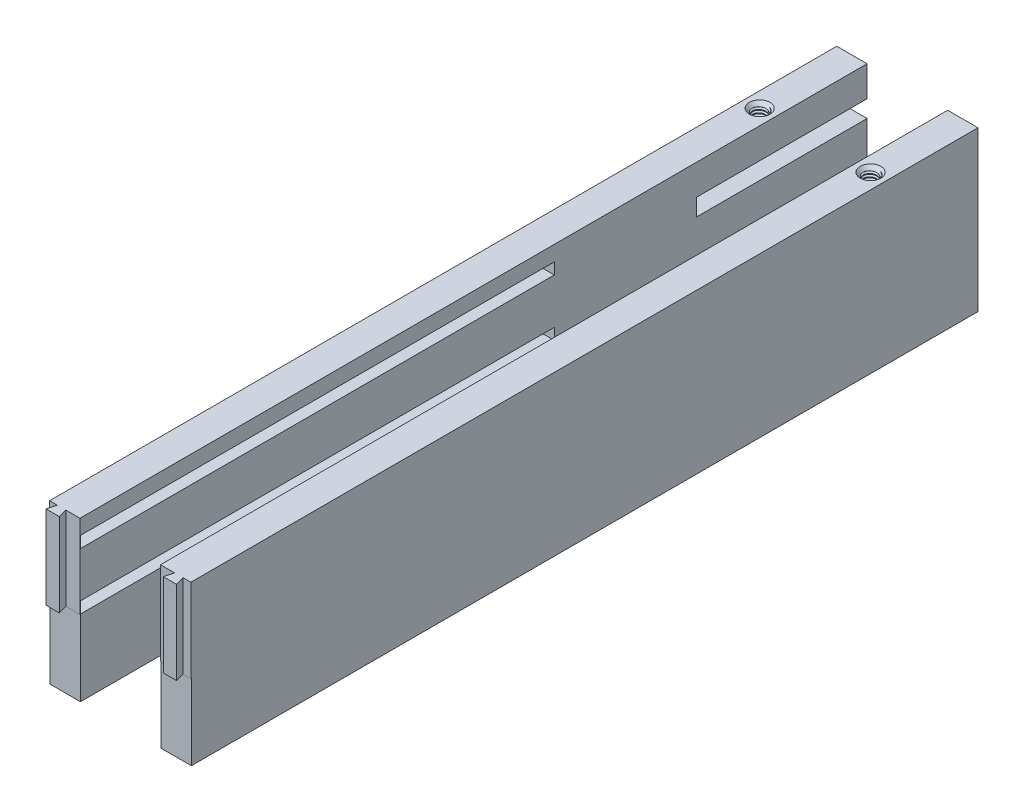
SolidWorks part; units mm, degrees
ref_plane "Front Plane" through (0, 0, 0) normal (0, 0, 1) x (1, 0, 0)
ref_plane "Top Plane" through (0, 0, 0) normal (0, 1, 0) x (1, 0, 0)
ref_plane "Right Plane" through (0, 0, 0) normal (1, 0, 0) x (0, 0, -1)
sketch "Sketch1" plane through (0, 0, 0) normal (1, 0, 0) x (0, 0, -1)
  line L1 (-64.8048, 9.1795) -> (145.1952, 9.1795)
  line L2 (-64.8048, 9.1795) -> (-64.8048, -32.8205)
  line L3 (-64.8048, -32.8205) -> (145.1952, -32.8205)
  line L4 (145.1952, 9.1795) -> (145.1952, -32.8205)
  dimension "D1" = 210
  dimension "D2" = 42
extrude "Boss-Extrude1" add sketch "Sketch1" along normal blind 8 contours L2 L3 L4 L1
sketch "Sketch12" plane through (0, 9.1795, 0) normal (0, 1, 0) x (1, 0, 0)
  line L0 (0, -62.4548) -> (2.0297, -62.4548)
  line L1 (0, -64.8048) -> (0, 145.1952) construction
  line L2 (2.0297, -62.4548) -> (1.4, -64.8048)
  line L3 (8, -64.8048) -> (0, -64.8048) construction
  line L4 (1.4, -64.8048) -> (0, -64.8048)
  line L5 (0, -64.8048) -> (0, -62.4548)
  line L6 (8, -62.4548) -> (8, -64.8048)
  line L7 (8, -64.8048) -> (8, 145.1952) construction
  line L8 (8, -64.8048) -> (4.9094, -64.8048)
  line L9 (4.9094, -64.8048) -> (4.2797, -62.4548)
  line L10 (4.2797, -62.4548) -> (8, -62.4548)
  dimension "D1" = 2.35
  dimension "D3" = 105
  dimension "D4" = 105
  dimension "D5" = 2.25
  dimension "D6" = 1.4
extrude "Cut-Extrude8" cut sketch "Sketch12" against normal blind 25
sketch "Sketch13" plane through (0, -32.8205, 0) normal (0, -1, 0) x (1, 0, 0)
  line L0 (8, 64.8048) -> (8, -145.1952) construction
  line L1 (0, 64.8048) -> (8, 64.8048)
  line L2 (0, 64.8048) -> (0, 62.3048)
  line L3 (0, 62.3048) -> (8, 62.3048)
  line L4 (8, 64.8048) -> (8, 62.3048)
  dimension "D1" = 2.5
extrude "Cut-Extrude9" cut sketch "Sketch13" against normal blind 20
sketch "Sketch43" plane through (8, 0, 0) normal (1, 0, 0) x (0, 0, -1)
  line L0 (145.1952, -32.8205) -> (145.1952, -27.8205) construction
  line L2 (145.1952, -27.8205) -> (140.1952, -27.8205) construction
  line L3 (140.1952, -27.8205) -> (140.1952, -12.8205)
  line L4 (140.1952, -12.8205) -> (135.1952, -12.8205)
  line L5 (135.1952, -12.8205) -> (135.1952, -27.8205)
  line L6 (135.1952, -27.8205) -> (140.1952, -27.8205)
  dimension "D1" = 15
  dimension "D2" = 5
  dimension "D3" = 5
  dimension "D4" = 5
extrude "Boss-Extrude8" add sketch "Sketch43" along normal blind 6
sketch "Sketch44" plane through (8, 0, 0) normal (1, 0, 0) x (0, 0, -1)
  line L0 (145.1952, -32.8205) -> (130.1952, -32.8205) construction
  line L1 (-62.3048, -32.8205) -> (145.1952, -32.8205) construction
  line L2 (130.1952, -32.8205) -> (130.1952, -26.8205)
  line L3 (130.1952, -26.8205) -> (115.1952, -26.8205)
  line L4 (115.1952, -26.8205) -> (115.1952, -32.8205)
  line L5 (115.1952, -32.8205) -> (130.1952, -32.8205)
  dimension "D1" = 15
  dimension "D2" = 15
  dimension "D3" = 6
extrude "Boss-Extrude9" add sketch "Sketch44" along normal blind 6
sketch "Sketch46" plane through (0, 0, 62.3048) normal (0, 0, 1) x (1, 0, 0)
  line L0 (8, 9.1795) -> (8, 5.1795) construction
  line L1 (8, -12.8205) -> (8, 9.1795) construction
  line L2 (8, 5.1795) -> (8, 2.1795)
  line L3 (8, 2.1795) -> (8, -9.7705) construction
  line L4 (8, -9.7705) -> (8, -12.7705)
  line L5 (8, 5.1795) -> (4.9094, 5.1795)
  line L6 (4.9094, -12.8205) -> (4.9094, 9.1795) construction
  line L7 (4.9094, 5.1795) -> (4.9094, 2.1795)
  line L8 (4.9094, 2.1795) -> (8, 2.1795)
  line L9 (8, -9.7705) -> (4.813, -9.7705)
  line L10 (4.813, -9.7705) -> (4.9094, -12.7705)
  line L11 (4.9094, -12.7705) -> (8, -12.7705)
  dimension "D1" = 4
  dimension "D2" = 3
  dimension "D3" = 11.95
  dimension "D4" = 3
extrude "Cut-Extrude15" cut sketch "Sketch46" against normal blind 125
ref_plane "Plane1" through (18.625, 0, 0) normal (-1, 0, 0) x (0, 0, 1)
sketch "Sketch23" plane through (0, 0, -145.1952) normal (0, 0, -1) x (-1, 0, 0)
  line L0 (-8, -32.8205) -> (-8, -3.3205)
  line L1 (-8, 9.1795) -> (-8, -32.8205) construction
  line L3 (-8, -3.3205) -> (-3.5, -3.3205)
  line L4 (-8, -3.3205) -> (-8, 1.1795)
  line L5 (-8, 1.1795) -> (-3.5, 1.1795)
  line L6 (-3.5, -3.3205) -> (-3.5, 1.1795)
  line M5 (-8, 9.1795) -> (-8, -32.8205)
  dimension "D1" = 4.5
  dimension "D2" = 4.5
  dimension "D3" = 29.5
extrude "Cut-Extrude14" cut sketch "Sketch23" against normal blind 45 contours L3 L6 L5 M5 region at (5.75, -1.0705, -145.1952)
mirror "Mirror4" about plane through (18.625, 0, 0) normal (-1, 0, 0) of bodies 121 113
sketch "Sketch30" plane through (0, 9.1795, 0) normal (0, 1, 0) x (1, 0, 0)
  line L0 (0, -62.4548) -> (0, 145.1952) construction
  line L1 (37.25, -62.4548) -> (37.25, 145.1952) construction
  line L2 (4, 120.8538) -> (33.25, 120.8538) construction
  circle A0 centre (4, 120.8538) radius 2
  circle A1 centre (33.25, 120.8538) radius 2
  dimension "D1" = 4
  dimension "D2" = 4
hole_wizard "#8-32 Tapped Hole1" positions "Sketch35" profile "Sketch37" tap size "#8-32" standard "ANSI Inch"
sketch "Sketch35" plane through (0, 9.1795, 0) normal (0, 1, 0) x (1, 0, 0)
  point P0 (33.25, 120.8538)
  point P3 (4, 120.8538)
sketch "Sketch37" plane through (33.25, 9.1795, -120.8538) normal (1, 0, 0) x (0, 0, 1)
  line L0 (0, 0) -> (0, 10.7074)
  line L1 (0, 10.7074) -> (1.7272, 9.6696)
  line L2 (1.7272, 9.6696) -> (1.7272, 0.9906)
  line L3 (1.7272, 0.9906) -> (2.7178, 0)
  line L5 (2.7178, 0) -> (0, 0)
  line L6 (-1.7272, 0.9906) -> (-2.7178, 0) construction
  line L10 (0, 10.7074) -> (-1.7272, 9.6696) construction
  line L11 (0, -6.35) -> (0, 107.95) construction
  dimension "Tap Drill Dia." = 3.4544
  dimension "Tap Drill Depth" = 10.7074
  dimension "Near C'Sink Dia." = 5.4356
  dimension "Near C'Sink Angle" = 90
  dimension "Drill Angle" = 118
cosmetic thread "Hole Thread2" parameters "D1"=8.33, "D2"=4.1656
cosmetic thread "Hole Thread6" parameters "D1"=8.33, "D2"=4.1656
thread "Thread3" pitch 0.7937 method cut profile "Thread Profile5" start angle 0, offset 1, length 10, pitch 0.7937, diameter 3.4544
ref_plane "Plane6" through (31.5228, 9.1889, -120.8538) normal (0, 0, 1) x (-1, 0, 0)
sketch "Thread Profile5" plane through (31.5228, 9.1889, -120.8538) normal (0, 0, 1) x (-1, 0, 0)
  line L0 (0, 0) -> (0, 0.7937) construction
  line L1 (0, 0) -> (0.4296, 0.248)
  line L2 (0.4296, 0.248) -> (0.4296, 0.3473)
  line L3 (0.4296, 0.3473) -> (0, 0.5953)
  line L4 (0.4296, 0.2977) -> (0, 0.2977) construction
  line L11 (0, 0) -> (0, 0.5953)
  point P2 (0, 0)
  dimension "Pitch" = 0.7937
  dimension "Profile_Angle" = 60
  dimension "Profile_Land" = 0.0992
  dimension "Profile_Height" = 0.4296
thread "Thread4" pitch 0.7937 method cut profile "Thread Profile6" start angle 0, offset 1, length 10, pitch 0.7937, diameter 3.4544
ref_plane "Plane7" through (2.2728, 9.1889, -120.8538) normal (0, 0, 1) x (-1, 0, 0)
sketch "Thread Profile6" plane through (2.2728, 9.1889, -120.8538) normal (0, 0, 1) x (-1, 0, 0)
  line L0 (0, 0) -> (0, 0.7937) construction
  line L1 (0, 0) -> (0.4296, 0.248)
  line L2 (0.4296, 0.248) -> (0.4296, 0.3473)
  line L3 (0.4296, 0.3473) -> (0, 0.5953)
  line L4 (0.4296, 0.2977) -> (0, 0.2977) construction
  line L11 (0, 0) -> (0, 0.5953)
  point P2 (0, 0)
  dimension "Pitch" = 0.7937
  dimension "Profile_Angle" = 60
  dimension "Profile_Land" = 0.0992
  dimension "Profile_Height" = 0.4296
